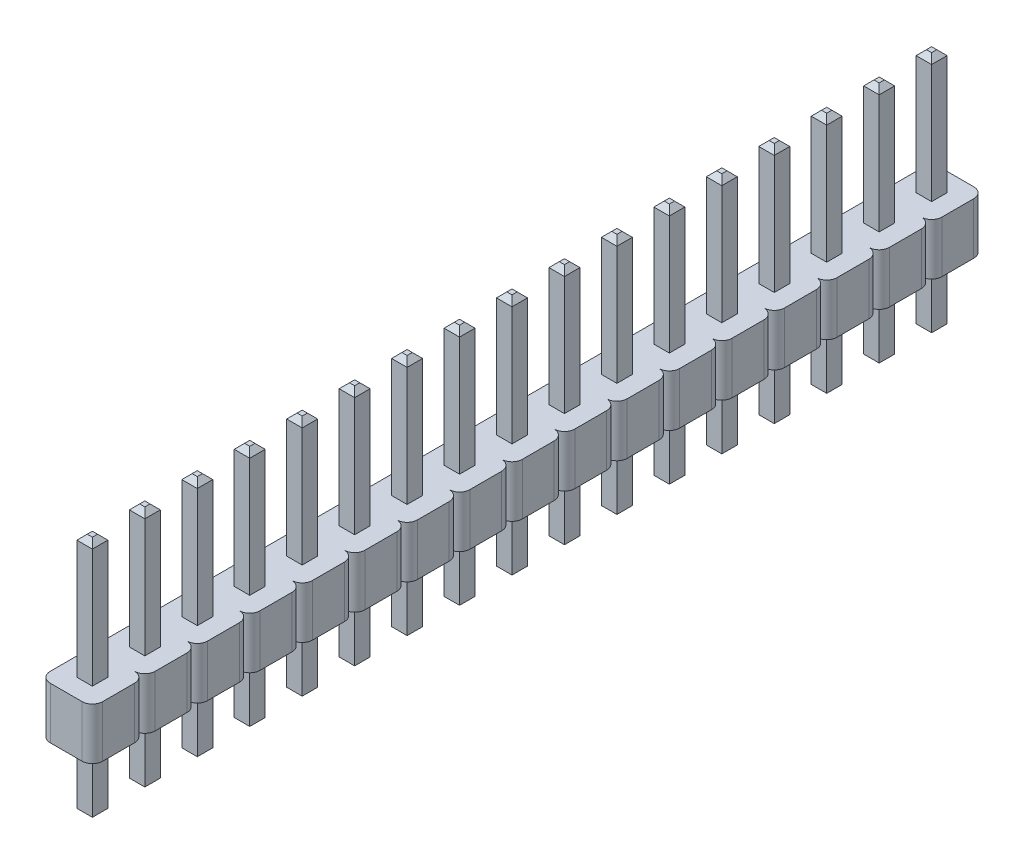
SolidWorks part; units mm, degrees
note: '?' marks a value the reader was unsure of.
ref_plane "Front Plane" through (0, 0, 0) normal (0, 0, 1) x (1, 0, 0)
ref_plane "Top Plane" through (0, 0, 0) normal (0, 1, 0) x (1, 0, 0)
ref_plane "Right Plane" through (0, 0, 0) normal (1, 0, 0) x (0, 0, -1)
ref_plane "Plane1" through (0, 0, 0) normal (0, 1, 0) x (-1, 0, 0)
sketch "Sketch1" plane through (0, 0, 0) normal (0, 1, 0) x (-1, 0, 0)
  line L0 (-0.77, 1.27) -> (0.77, 1.27)
  line L1 (1.27, 0.77) -> (1.27, -0.77)
  line L2 (0.77, -1.27) -> (-0.77, -1.27)
  line L3 (-1.27, -0.77) -> (-1.27, 0.77)
  line L4 (-0.77, 0.77) -> (0.77, -0.77) construction
  arc A0 (1.27, 0.77) -> (0.77, 1.27) centre (0.77, 0.77) ccw
  arc A1 (0.77, -1.27) -> (1.27, -0.77) centre (0.77, -0.77) ccw
  arc A2 (-1.27, -0.77) -> (-0.77, -1.27) centre (-0.77, -0.77) ccw
  arc A3 (-0.77, 1.27) -> (-1.27, 0.77) centre (-0.77, 0.77) ccw
  dimension "D3" = 0.5
  dimension "D2" = 2.54
extrude "Boss-Extrude1" add sketch "Sketch1" along normal blind 2.5
ref_plane "Plane2" through (0.77, 0, 1.27) normal (-1, 0, 0) x (0, 0, 1)
ref_plane "Plane3" through (0.77, 0, 1.27) normal (0, -1, 0) x (0, 0, 1)
ref_axis "Axis1" through (0.77, 0, -79.63) along (0, 0, 1)?
ref_plane "Plane4" through (0, 0, 0) normal (0, 1, 0) x (-1, 0, 0)
sketch "Sketch2" plane through (0, 0, 0) normal (0, 1, 0) x (-1, 0, 0)
  line L0 (-0.375, 0.375) -> (0.375, 0.375)
  line L1 (0.375, 0.375) -> (0.375, -0.375)
  line L2 (0.375, -0.375) -> (-0.375, -0.375)
  line L3 (-0.375, -0.375) -> (-0.375, 0.375)
  line L4 (-0.375, 0.375) -> (0.375, -0.375) construction
  dimension "D1" = 0.75
extrude "Boss-Extrude2" add sketch "Sketch2" along normal blind 8.5 and the other way blind 3.25
ref_plane "Plane5" through (0.3725, 0, 0.3725) normal (-1, 0, 0) x (0, 0, 1)
ref_plane "Plane6" through (0.3725, 0, 0.3725) normal (0, -1, 0) x (0, 0, 1)
ref_axis "Axis2" through (0.3725, 0, -80.5275) along (0, 0, 1)?
chamfer "Chamfer1" distance 0.25 angle 45 8 edges at (0, -3.25, 0.375) (-0.375, -3.25, 0) (0.375, -3.25, 0) (0, -3.25, -0.375) (0, 8.5, 0.375) (-0.375, 8.5, 0) (0, 8.5, -0.375) (0.375, 8.5, 0)
ref_axis "Axis3" through (0, -3.575, 0) along (0, 1, 0)?
pattern_linear "LPattern1" count 17 spacing 2.54 along (0, 0, -1) of "Boss-Extrude2", "Boss-Extrude1", "Chamfer1"
